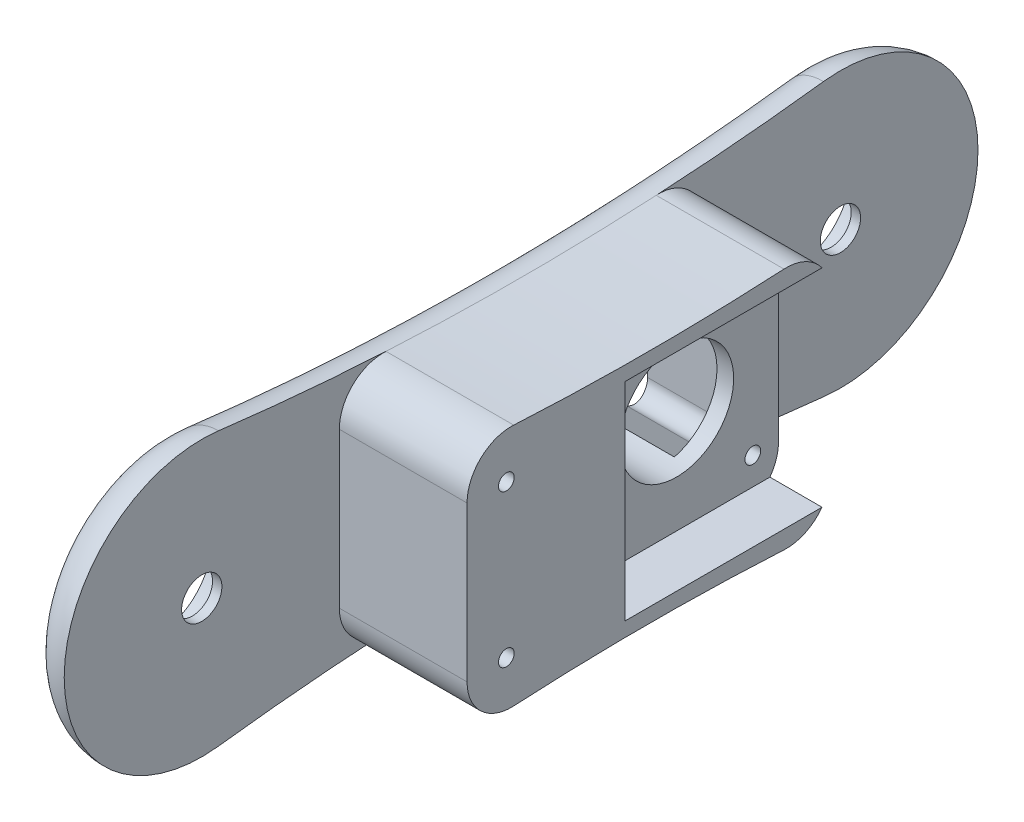
SolidWorks part; units mm, degrees
ref_plane "Front Plane" through (0, 0, 0) normal (0, 0, 1) x (1, 0, 0)
ref_plane "Top Plane" through (0, 0, 0) normal (0, 1, 0) x (1, 0, 0)
ref_plane "Right Plane" through (0, 0, 0) normal (1, 0, 0) x (0, 0, -1)
sketch "Sketch1" plane through (0, 0, 0) normal (1, 0, 0) x (0, 0, -1)
  line L0 (-188.563, 0) -> (207.6309, 0) construction
  circle A0 centre (-130, 0) radius 28
  circle A1 centre (0, 0) radius 28
  arc A2 (-126.5668, 27.7887) -> (-3.4332, 27.7887) centre (-65, 526.125) ccw
  arc A3 (-126.5668, -27.7887) -> (-3.4332, -27.7887) centre (-65, -526.125) cw
  point P13 (-65, 24)
  point P14 (-65, -24)
  dimension "D1" = 56
  dimension "D2" = 56
  dimension "D3" = 130
  dimension "D4" = 48
extrude "Boss-Extrude1" add sketch "Sketch1" along normal blind 35 contours A1 L0 | L0 A1 | A0 L0 A1 A2 | L0 A0 A3 A1 | L0 A0 | A0 L0 region at (0, 11.8836, 130) region at (0, -11.8836, 130) region at (0, 13.2362, 65) region at (0, -13.2362, 65) region at (0, 11.8836, 0) region at (0, -11.8836, 0)
sketch "Sketch4" plane through (0, 0, 0) normal (0, 1, 0) x (1, 0, 0)
  line L0 (-64.695, -65) -> (222.9919, -65) construction
  line L1 (9, 28) -> (61, 28)
  line L2 (9, 28) -> (9, -28)
  line L3 (9, -28) -> (61, -28)
  line L4 (61, 28) -> (61, -28)
  line L5 (9, 28) -> (61, -28) construction
  line L6 (9, -28) -> (61, 28) construction
  line L7 (9, -102) -> (61, -158) construction
  line L8 (9, -158) -> (61, -102) construction
  line L9 (61, -158) -> (61, -102)
  line L10 (9, -102) -> (61, -102)
  line L11 (9, -158) -> (9, -102)
  line L12 (9, -158) -> (61, -158)
  point P0 (35, 0)
  point P12 (35, -130)
  dimension "D1" = 56
  dimension "D2" = 52
  dimension "D3" = 35
  dimension "D4" = 65
extrude "Cut-Extrude1" cut sketch "Sketch4" against normal through all both and the other way through all
sketch "Sketch5" plane through (0, 0, 0) normal (1, 0, 0) x (0, 0, -1)
  line L1 (-33.225, -15.5) -> (-64.225, -15.5) construction
  line L2 (-33.225, -15.5) -> (-33.225, 15.5) construction
  line L3 (-33.225, 15.5) -> (-64.225, 15.5) construction
  line L4 (-64.225, -15.5) -> (-64.225, 15.5) construction
  line L5 (-33.225, -15.5) -> (-64.225, 15.5) construction
  line L6 (-33.225, 15.5) -> (-64.225, -15.5) construction
  circle A8 centre (-33.225, -15.5) radius 1.6
  circle A9 centre (-33.225, 15.5) radius 1.6
  circle A10 centre (-64.225, -15.5) radius 1.6
  circle A11 centre (-64.225, 15.5) radius 1.6
  circle A12 centre (-33.225, -15.5) radius 3
  circle A13 centre (-33.225, 15.5) radius 3
  circle A14 centre (-64.225, -15.5) radius 3
  circle A15 centre (-64.225, 15.5) radius 3
  point P0 (-48.725, 0)
  dimension "D4" = 3.2
  dimension "D5" = 6
  dimension "D1" = 48.725
  dimension "D2" = 31
  dimension "D3" = 31
sketch "Sketch6" plane through (0, 0, 0) normal (1, 0, 0) x (0, 0, -1)
  line L1 (-27.625, -21.1) -> (-69.825, -21.1)
  line L2 (-27.625, -21.1) -> (-27.625, 21.1)
  line L3 (-27.625, 21.1) -> (-69.825, 21.1)
  line L4 (-69.825, -21.1) -> (-69.825, 21.1)
  line L5 (-27.625, -21.1) -> (-69.825, 21.1) construction
  line L6 (-27.625, 21.1) -> (-69.825, -21.1) construction
  point P0 (-48.725, 0)
  dimension "D1" = 48.725
  dimension "D2" = 42.2
  dimension "D3" = 42.2
sketch "Sketch7" plane through (0, 0, 0) normal (1, 0, 0) x (0, 0, -1)
  circle A0 centre (0, 0) radius 4.1
  circle A1 centre (-130, 0) radius 4.1
  circle A2 centre (0, 0) radius 11
  circle A3 centre (-130, 0) radius 11
  dimension "D3" = 130
  dimension "D1" = 8.2
  dimension "D2" = 22
ref_plane "Plane1" through (35, 0, 0) normal (1, 0, 0) x (0, 0, -1)
extrude "Cut-Extrude2" cut sketch "Sketch6" against normal blind 10.61 from surface starting at face at (35, 0, 65)
extrude "Cut-Extrude3" cut sketch "Sketch5" along normal through all contours A10 | A11 | A9 | A8
extrude "Cut-Extrude4" cut sketch "Sketch5<3>" along normal blind 21 contours A12 | A13 | A15 | A14
sketch "Sketch5<3>" plane through (0, 0, 0) normal (1, 0, 0) x (0, 0, -1) same geometry as "Sketch5"
sketch "Sketch8" plane through (0, 0, 0) normal (1, 0, 0) x (0, 0, -1)
  line L0 (0, 0) -> (-148.5261, 0) construction
  circle A0 centre (-94, -15.5) radius 1.6
  circle A1 centre (-94, 15.5) radius 1.6
  circle A2 centre (-94, -15.5) radius 3
  circle A3 centre (-94, 15.5) radius 3
  dimension "D1" = 3.2
  dimension "D2" = 6
  dimension "D3" = 94
  dimension "D4" = 31
extrude "Cut-Extrude5" cut sketch "Sketch8" along normal through all contours A0 | A1
extrude "Cut-Extrude6" cut sketch "Sketch8<3>" along normal blind 25 contours A2 | A3
sketch "Sketch8<3>" plane through (0, 0, 0) normal (1, 0, 0) x (0, 0, -1) same geometry as "Sketch8"
extrude "Cut-Extrude7" cut sketch "Sketch7" along normal up to next contours A0 | A1
extrude "Cut-Extrude8" cut sketch "Sketch7<3>" along normal blind 7.1 contours A2 | A3
sketch "Sketch7<3>" plane through (0, 0, 0) normal (1, 0, 0) x (0, 0, -1) same geometry as "Sketch7"
sketch "Sketch9" plane through (0, 0, 0) normal (1, 0, 0) x (0, 0, -1)
  line L1 (0, 0) -> (-81.7068, 0) construction
  line L4 (-34.8065, -18.0493) -> (-52.9424, -6.7981)
  line L5 (-34.8065, 18.0493) -> (-52.9424, 6.7981)
  line L6 (-30.225, -15.5) -> (-30.225, 15.5)
  circle A0 centre (0, 0) radius 28 construction
  circle A1 centre (-48.725, 0) radius 8
  circle A3 centre (-33.225, -15.5) radius 3
  circle A4 centre (-33.225, 15.5) radius 3
  arc A5 (-30.6269, -14) -> (-30.6269, 14) centre (-6.3782, 0) cw construction
  arc A6 (-52.9424, -6.7981) -> (-52.9424, 6.7981) centre (-48.725, 0) cw
  point P30 (-63.9002, 0)
  dimension "D1" = 56
  dimension "D2" = 16
  dimension "D5" = 6
  dimension "D6" = 28
  dimension "D7" = 8
  dimension "D3" = 48.725
  dimension "D8" = 48.725
extrude "Cut-Extrude9" cut sketch "Sketch9" along normal up to surface (21 mm away) contours A6 L4 A3 A5 A4 L5 A1 | A1 region at (0, 0, 37.6008) region at (0, 0, 48.725) up to face at (21, -15.5, 31.625)
sketch "Sketch11" plane through (0, 0, 0) normal (1, 0, 0) x (0, 0, -1)
  circle A0 centre (-48.725, 0) radius 11.6
  dimension "D1" = 23.2
  dimension "D2" = 48.725
extrude "Cut-Extrude11" cut sketch "Sketch11" against normal through all from surface starting at face at (24.39, -15.5, 34.825)
fillet "Fillet3" radius 9 4 edges at (0, 0, 158) (0, -24, 65) (0, 0, -28) (0, 24, 65)
fillet "Fillet4" radius 9 4 edges at (22, -25.3651, 28) (22, -25.3651, 102) (22, 25.3651, 102) (22, 25.3651, 28)
equation "\"top dia\"= 56"
equation "\"D1@Sketch1\"=\"top dia\""
equation "\"bottom dia\"= 56"
equation "\"D2@Sketch1\"=\"bottom dia\""
equation "\"arm length\"= 130"
equation "\"D3@Sketch1\"=\"arm length\""
equation "\"across\"= 48"
equation "\"D4@Sketch1\"=\"across\""
equation "\"arm width\"=70"
equation "\"D1@Boss-Extrude1\"=\"arm width\"/2"
equation "\"D1@Sketch4\"=\"bottom dia\""
equation "\"D2@Sketch4\"=\"arm width\" - (7+2)*2"
equation "\"D3@Sketch4\"=\"arm width\"/2"
equation "\"D4@Sketch4\"=\"arm length\"/2"
equation "\"gear dist\"= 48.725"
equation "\"D1@Sketch5\"=\"gear dist\""
equation "\"D1@Sketch6\"=\"gear dist\""
equation "\"D3@Sketch7\"=\"arm length\" "
equation "\"D1@Plane1\"= \"arm width\" / 2"
equation "\"D3@Sketch8\"=\"arm length\" - \"top dia\"/2 - 8"
equation "\"stepper hole dist\"= 31"
equation "\"D2@Sketch5\"= \"stepper hole dist\""
equation "\"D3@Sketch5\"= \"stepper hole dist\""
equation "\"D4@Sketch8\"= \"stepper hole dist\""
equation "\"D1@Sketch9\"=\"bottom dia\""
equation "\"M3 hole size\"= 3.2"
equation "\"D4@Sketch5\"= \"M3 hole size\""
equation "\"M3 bolt head\"= 6"
equation "\"D5@Sketch5\"= \"M3 bolt head\""
equation "\"stepper motor width\"= 42.2"
equation "\"D2@Sketch6\"= \"stepper motor width\""
equation "\"D3@Sketch6\"= \"stepper motor width\""
equation "\"bearing bore\"= 8.2"
equation "\"bearing OD\"= 22"
equation "\"D1@Sketch7\"= \"bearing bore\""
equation "\"D2@Sketch7\"= \"bearing OD\""
equation "\"D1@Sketch8\"=\"M3 hole size\""
equation "\"D2@Sketch8\"=\"M3 bolt head\""
equation "\"D3@Sketch9\"=\"gear dist\""
equation "\"D5@Sketch9\"=\"M3 bolt head\""
equation "\"D2@Sketch11\"=\"gear dist\""
equation "\"gear extension OD\"=23.2"
equation "\"D1@Sketch11\"= \"gear extension OD\""
equation "\"stepper motor cut depth\"=10.61"
equation "\"D1@Cut-Extrude2\"=\"stepper motor cut depth\""
equation "\"bearing depth\"=7.1"
equation "\"D1@Cut-Extrude8\"=\"bearing depth\""
equation "\"D8@Sketch9\"= \"gear dist\""
